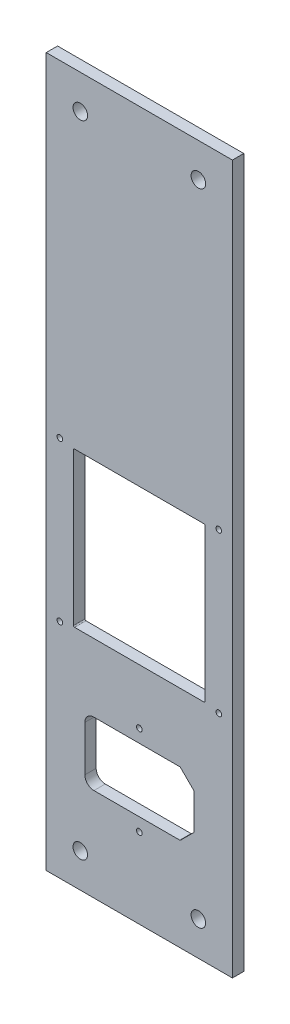
SolidWorks part; units mm, degrees
ref_plane "Front Plane" through (0, 0, 0) normal (0, 0, 1) x (1, 0, 0)
ref_plane "Top Plane" through (0, 0, 0) normal (0, 1, 0) x (1, 0, 0)
ref_plane "Right Plane" through (0, 0, 0) normal (1, 0, 0) x (0, 0, -1)
sketch "Sketch1" plane through (0, 0, 0) normal (0, 0, 1) x (1, 0, 0)
  line L1 (-41, -156) -> (41, -156)
  line L2 (-41, -156) -> (-41, 156)
  line L3 (-41, 156) -> (41, 156)
  line L4 (41, -156) -> (41, 156)
  line L5 (-41, -156) -> (41, 156) construction
  line L6 (-41, 156) -> (41, -156) construction
  point P0 (0, 0)
  dimension "D1" = 312
  dimension "D2" = 82
extrude "Boss-Extrude1" add sketch "Sketch1" along normal blind 5
sketch "Sketch2" plane through (0, 0, 5) normal (0, 0, 1) x (1, 0, 0)
  line L0 (0, -1000) -> (0, 49000) construction
  line L1 (-24, -115) -> (24, -115)
  line L2 (-24, -115) -> (-24, -87)
  line L3 (-24, -87) -> (24, -87)
  line L4 (24, -115) -> (24, -87)
  line L5 (-24, -115) -> (24, -87) construction
  line L6 (-24, -87) -> (24, -115) construction
  line L7 (-41, -156) -> (41, -156) construction
  circle A0 centre (0, -81.25) radius 1.25
  circle A1 centre (0, -120.75) radius 1.25
  point P0 (0, -101)
  dimension "D6" = 2.5
  dimension "D7" = 2.5
  dimension "D1" = 28
  dimension "D2" = 48
  dimension "D3" = 55
  dimension "D4" = 19.75
  dimension "D5" = 19.75
extrude "Cut-Extrude1" cut sketch "Sketch2" against normal blind 10
chamfer "Chamfer1" distance 6 angle 45 2 edges at (24, -115, 2.5) (24, -87, 2.5)
fillet "Fillet1" radius 4 2 edges at (-24, -115, 2.5) (-24, -87, 2.5)
sketch "Sketch3" plane through (0, 0, 5) normal (0, 0, 1) x (1, 0, 0)
  line L0 (0, -1000) -> (0, 49000) construction
  line L1 (18, -87) -> (-20, -87) construction
  line L2 (-29, -57) -> (29, -57)
  line L3 (-29, -57) -> (-29, 11)
  line L4 (-29, 11) -> (29, 11)
  line L5 (29, -57) -> (29, 11)
  line L6 (-29, -57) -> (29, 11) construction
  line L7 (-29, 11) -> (29, -57) construction
  point P1 (0, -23)
  dimension "D1" = 58
  dimension "D2" = 68
  dimension "D3" = 30
extrude "Cut-Extrude2" cut sketch "Sketch3" against normal through all
hole_wizard "M3x0.5 Tapped Hole1" positions "Sketch7" profile "Sketch6" tap size "M3x0.5" standard "ANSI Metric" end condition through all
sketch "Sketch7" plane through (0, 0, 5) normal (0, 0, 1) x (1, 0, 0)
  line L0 (0, -23) -> (0, -57) construction
  line L1 (-29, -23) -> (29, -23) construction
  line L2 (-29, -57) -> (29, -57) construction
  line L3 (-29, 11) -> (-29, -57) construction
  point P7 (-35, 12)
  point P8 (35, 12)
  point P9 (35, -58)
  point P10 (-35, -58)
  dimension "D1" = 35
  dimension "D2" = 35
  dimension "D3" = 35
  dimension "D4" = 35
  dimension "D5" = 35
  dimension "D6" = 35
  dimension "D7" = 35
  dimension "D8" = 35
sketch "Sketch6" plane through (-35, 12, 5) normal (1, 0, 0) x (0, -1, 0)
  line L0 (0, 0) -> (0, 5)
  line L1 (0, 5) -> (1.25, 5)
  line L2 (1.25, 5) -> (1.25, 0)
  line L5 (1.25, 0) -> (0, 0)
  line L11 (0, -6.35) -> (0, 107.95) construction
  dimension "Thru Tap Drill Dia." = 2.5
  dimension "Thru Tap Drill Depth" = 5
cosmetic thread "Hole Thread1" parameters "D2"=3
cosmetic thread "Hole Thread2" parameters "D2"=3
cosmetic thread "Hole Thread3" parameters "D2"=3
cosmetic thread "Hole Thread4" parameters "D2"=3
fillet "Fillet2" radius 0.5 8 edges at (18, -115, 2.5) (24, -109, 2.5) (24, -93, 2.5) (18, -87, 2.5) (29, -57, 2.5) (-29, -57, 2.5) (-29, 11, 2.5) (29, 11, 2.5)
hole_wizard "M6 Clearance Hole1" positions "Sketch9" profile "Sketch8" hole size "M6" standard "ANSI Metric"
sketch "Sketch9" plane through (0, 0, 5) normal (0, 0, 1) x (1, 0, 0)
  line L0 (-1001.3858, -141) -> (48998.6142, -141) construction
  line L2 (-984.103, 141) -> (49015.897, 141) construction
  line L3 (41, 156) -> (-41, 156) construction
  line L4 (-41, -156) -> (41, -156) construction
  line L5 (-26, -959.2936) -> (-26, 49040.7064) construction
  line L6 (26, -949.525) -> (26, 49050.475) construction
  line L7 (-41, 156) -> (-41, -156) construction
  line L8 (41, -156) -> (41, 156) construction
  point P23 (-26, 141)
  point P25 (26, 141)
  point P31 (-26, -141)
  point P33 (26, -141)
  dimension "D1" = 15
  dimension "D2" = 15
  dimension "D3" = 15
  dimension "D4" = 15
sketch "Sketch8" plane through (-26, 141, 5) normal (1, 0, 0) x (0, -1, 0)
  line L0 (0, 0) -> (0, 6.9228)
  line L1 (0, 6.9228) -> (3.2, 5)
  line L2 (3.2, 5) -> (3.2, 0)
  line L5 (3.2, 0) -> (0, 0)
  line L10 (0, 6.9228) -> (-3.2, 5) construction
  line L11 (0, -6.35) -> (0, 107.95) construction
  dimension "Hole Dia." = 6.4
  dimension "Hole Depth" = 5
  dimension "Drill Angle" = 118
